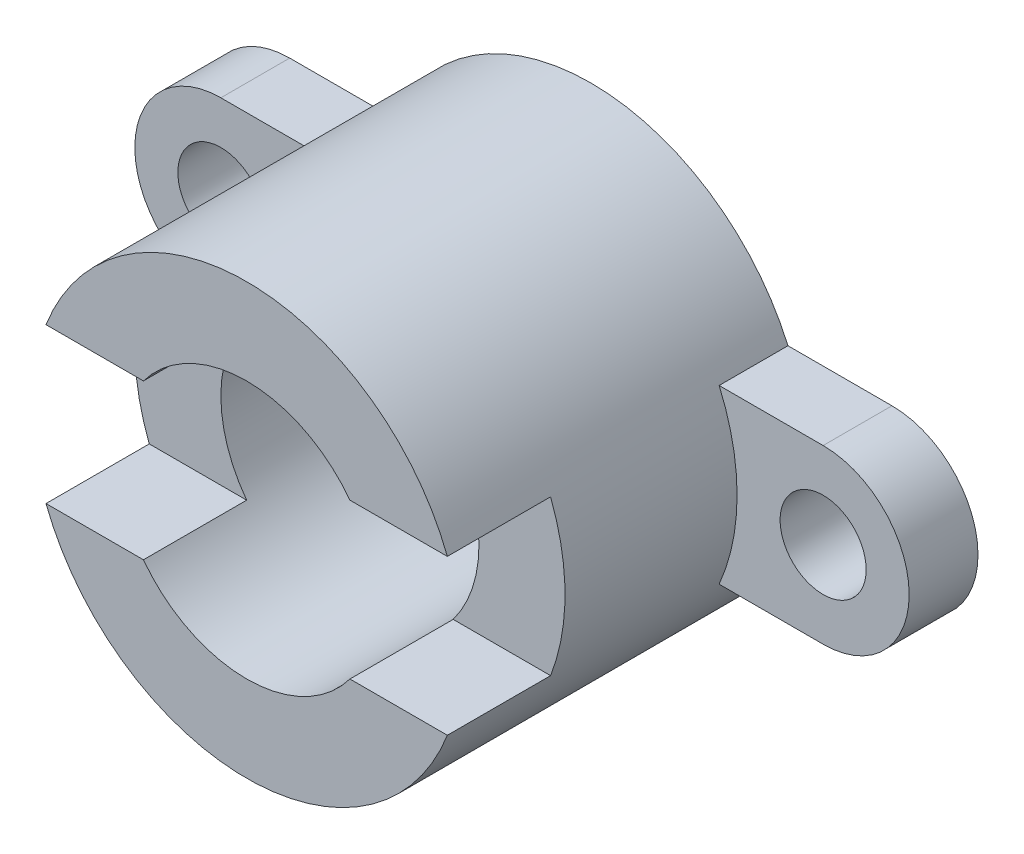
SolidWorks part; units mm, degrees
ref_plane "Front Plane" through (0, 0, 0) normal (0, 0, 1) x (1, 0, 0)
ref_plane "Top Plane" through (0, 0, 0) normal (0, 1, 0) x (1, 0, 0)
ref_plane "Right Plane" through (0, 0, 0) normal (1, 0, 0) x (0, 0, -1)
sketch "Sketch1" plane through (0, 0, 0) normal (0, 0, 1) x (1, 0, 0)
  line L0 (-83.3632, 0) -> (66.3971, 0) construction
  line L1 (0, 30.9887) -> (0, -30.7811) construction
  line L2 (-35, 10) -> (-22.9129, 10)
  line L3 (-35, -10) -> (-22.9129, -10)
  line L4 (35, -10) -> (22.9129, -10)
  line L5 (35, 10) -> (22.9129, 10)
  arc A0 (-22.9129, -10) -> (22.9129, -10) centre (0, 0) ccw
  circle A1 centre (0, 0) radius 15
  arc A2 (-35, 10) -> (-35, -10) centre (-35, 0) ccw
  arc A3 (35, 10) -> (35, -10) centre (35, 0) cw
  arc A4 (22.9129, 10) -> (-22.9129, 10) centre (0, 0) ccw
  circle A5 centre (-35, 0) radius 5
  circle A6 centre (35, 0) radius 5
  arc A7 (-22.9129, 10) -> (-22.9129, -10) centre (0, 0) ccw
  arc A8 (22.9129, 10) -> (22.9129, -10) centre (0, 0) cw
  dimension "D1" = 50
  dimension "D2" = 30
  dimension "D4" = 10
  dimension "D3" = 20
  dimension "D5" = 70
extrude "Boss-Extrude5" add sketch "Sketch1" along normal blind 40 contours A8 A4 A7 A0 A1 region at (0, 24.2929, 0)
extrude "Boss-Extrude6" add sketch "Sketch1<12>" along normal blind 8 contours L5 A8 L4 A3 A6 | A7 L2 A2 L3 A5 region at (-28.9564, 9.702, 0) region at (28.9564, 9.702, 0)
sketch "Sketch1<12>" plane through (0, 0, 0) normal (0, 0, 1) x (1, 0, 0) same geometry as "Sketch1"
ref_plane "Plane1" through (25, 0, 0) normal (1, 0, 0) x (0, 0, -1)
sketch "Sketch2" plane through (25, 0, 0) normal (1, 0, 0) x (0, 0, -1)
  line L0 (16.3151, 0) -> (-66.7726, 0) construction
  line L1 (-40, 25) -> (-40, -25) construction
  line L2 (-40, 9) -> (-40, -9)
  line L3 (-40, 9) -> (-28, 9)
  line L4 (-28, 9) -> (-28, -9)
  line L5 (-28, -9) -> (-40, -9)
  dimension "D1" = 18
  dimension "D2" = 12
extrude "Cut-Extrude1" cut sketch "Sketch2" against normal blind 68 contours L2 L5 L4 L3
